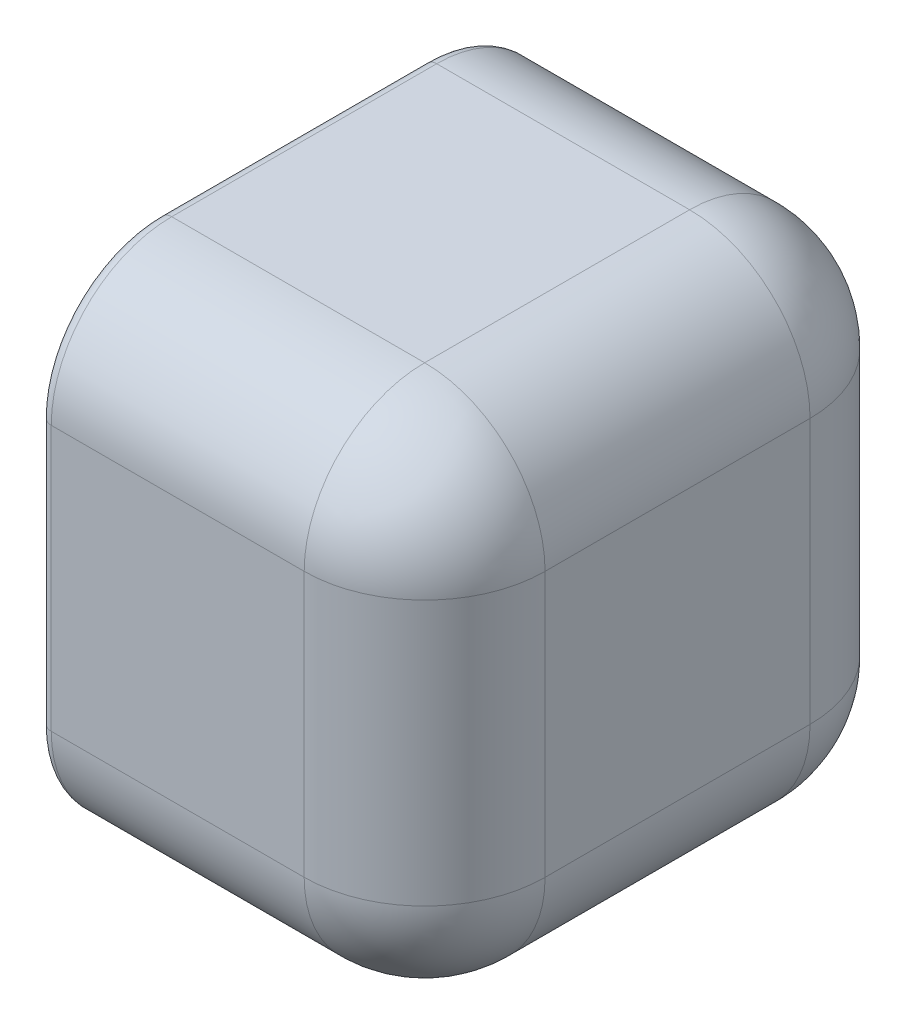
SolidWorks part; units mm, degrees
ref_plane "Plan de face" through (0, 0, 0) normal (0, 0, 1) x (1, 0, 0)
ref_plane "Plan de dessus" through (0, 0, 0) normal (0, 1, 0) x (1, 0, 0)
ref_plane "Plan de droite" through (0, 0, 0) normal (1, 0, 0) x (0, 0, -1)
sketch "Esquisse1" plane through (0, 0, 0) normal (0, 0, 1) x (1, 0, 0)
  line L1 (-21, -21) -> (21, -21)
  line L2 (-21, -21) -> (-21, 21)
  line L3 (-21, 21) -> (21, 21)
  line L4 (21, -21) -> (21, 21)
  line L5 (-21, -21) -> (21, 21) construction
  line L6 (-21, 21) -> (21, -21) construction
  point P0 (0, 0)
  dimension "D1" = 42
  dimension "D2" = 42
extrude "Boss.-Extru.1" add sketch "Esquisse1" along normal blind 42
fillet "Congé1" radius 10 12 edges at (0, -21, 0) (-21, -21, 21) (-21, 0, 0) (-21, 21, 21) (0, -21, 42) (-21, 0, 42) (21, 0, 42) (21, -21, 21) (21, 0, 0) (21, 21, 21) (0, 21, 42) (0, 21, 0)
sketch "Esquisse2" plane through (0, 0, 0) normal (0, 0, -1) x (-1, 0, 0)
  line L1 (5, -8) -> (-5, -8)
  line L2 (5, -8) -> (5, 8)
  line L3 (5, 8) -> (-5, 8)
  line L4 (-5, -8) -> (-5, 8)
  line L5 (5, -8) -> (-5, 8) construction
  line L6 (5, 8) -> (-5, -8) construction
  line L9 (1.55, -7) -> (-1.55, -7)
  line L10 (1.55, -7) -> (1.55, 7)
  line L11 (1.55, 7) -> (-1.55, 7)
  line L12 (-1.55, -7) -> (-1.55, 7)
  line L13 (1.55, -7) -> (-1.55, 7) construction
  line L14 (1.55, 7) -> (-1.55, -7) construction
  point P0 (0, 0)
  point P19 (0, 0)
  dimension "D1" = 16
  dimension "D2" = 10
  dimension "D3" = 14
  dimension "D4" = 3.1
sketch "Esquisse10" plane through (0, -21, 0) normal (0, -1, 0) x (-1, 0, 0)
  line L1 (11, -42) -> (21.1405, -42)
  line L2 (11, -42) -> (11, 0)
  line L3 (11, 0) -> (21.1405, 0)
  line L4 (21.1405, -42) -> (21.1405, 0)
  line L5 (11, -42) -> (21.1405, 0) construction
  line L6 (11, 0) -> (21.1405, -42) construction
  point P5 (16.0702, -21)
extrude "Enlèv. mat.-Extru.1" cut sketch "Esquisse10" against normal through all
sketch "Esquisse12" plane through (-11, 0, 0) normal (-1, 0, 0) x (0, 0, 1)
  line L0 (2.9289, 18.0711) -> (2.9289, -18.0711)
  line L1 (2.9289, -18.0711) -> (39.0711, -18.0711)
  line L2 (39.0711, -18.0711) -> (39.0711, 18.0711)
  line L3 (39.0711, 18.0711) -> (2.9289, 18.0711)
  line L5 (2.9289, 18.0711) -> (5.9289, 18.0711)
  line L6 (2.9289, 18.0711) -> (2.9289, 15.0711)
  line L7 (2.9289, 15.0711) -> (5.9289, 15.0711)
  line L8 (5.9289, 18.0711) -> (5.9289, 15.0711)
  line L9 (2.9289, 18.0711) -> (5.9289, 15.0711) construction
  line L10 (2.9289, 15.0711) -> (5.9289, 18.0711) construction
  line L11 (39.0711, -18.0711) -> (36.0711, -18.0711)
  line L12 (39.0711, -18.0711) -> (39.0711, -15.0711)
  line L13 (39.0711, -15.0711) -> (36.0711, -15.0711)
  line L14 (36.0711, -18.0711) -> (36.0711, -15.0711)
  line L15 (39.0711, -18.0711) -> (36.0711, -15.0711) construction
  line L16 (39.0711, -15.0711) -> (36.0711, -18.0711) construction
  arc A0 (10, 21) -> (0, 11) centre (10, 11) ccw construction
  arc A1 (0, -11) -> (10, -21) centre (10, -11) ccw construction
  arc A2 (32, -21) -> (42, -11) centre (32, -11) ccw construction
  arc A3 (42, 11) -> (32, 21) centre (32, 11) ccw construction
  point P19 (4.4289, 16.5711)
  point P23 (37.5711, -16.5711)
  dimension "D1" = 3
  dimension "D2" = 3
  dimension "D3" = 3
  dimension "D4" = 3
sketch "Esquisse14" plane through (-11, 0, 0) normal (-1, 0, 0) x (0, 0, 1)
  line L1 (5.9289, 15.0711) -> (36.0711, 15.0711)
  line L2 (5.9289, 15.0711) -> (5.9289, -15.0711)
  line L3 (5.9289, -15.0711) -> (36.0711, -15.0711)
  line L4 (36.0711, 15.0711) -> (36.0711, -15.0711)
  line L5 (5.9289, 15.0711) -> (36.0711, -15.0711) construction
  line L6 (5.9289, -15.0711) -> (36.0711, 15.0711) construction
  point P4 (21, 0)
extrude "Enlèv. mat.-Extru.5" cut sketch "Esquisse2" against normal blind 8 contours L10 L9 L12 L11
extrude "Enlèv. mat.-Extru.6" cut sketch "Esquisse14" against normal blind 22
sketch "Esquisse17" plane through (11, 0, 0) normal (-1, 0, 0) x (0, 0, 1)
  line L1 (5.9289, 15.0711) -> (9.9289, 15.0711)
  line L2 (5.9289, 15.0711) -> (5.9289, 11.0711)
  line L3 (5.9289, 11.0711) -> (9.9289, 11.0711)
  line L4 (9.9289, 15.0711) -> (9.9289, 11.0711)
  line L5 (5.9289, 15.0711) -> (9.9289, 11.0711) construction
  line L6 (5.9289, 11.0711) -> (9.9289, 15.0711) construction
  line L7 (36.0711, -15.0711) -> (32.0711, -15.0711)
  line L8 (36.0711, -15.0711) -> (36.0711, -11.5711)
  line L9 (36.0711, -11.5711) -> (32.0711, -11.5711)
  line L10 (32.0711, -15.0711) -> (32.0711, -11.5711)
  line L11 (36.0711, -15.0711) -> (32.0711, -11.5711) construction
  line L12 (36.0711, -11.5711) -> (32.0711, -15.0711) construction
  point P4 (7.9289, 13.0711)
  point P10 (34.0711, -13.3211)
  dimension "D1" = 4
  dimension "D2" = 4
  dimension "D3" = 4
  dimension "D4" = 3.5
sketch "Esquisse20" plane through (11, 0, 0) normal (-1, 0, 0) x (0, 0, 1)
  line L1 (36.0711, 15.0711) -> (32.0711, 15.0711)
  line L2 (36.0711, 15.0711) -> (36.0711, 11.5711)
  line L3 (36.0711, 11.5711) -> (32.0711, 11.5711)
  line L4 (32.0711, 15.0711) -> (32.0711, 11.5711)
  line L5 (36.0711, 15.0711) -> (32.0711, 11.5711) construction
  line L6 (36.0711, 11.5711) -> (32.0711, 15.0711) construction
  point P4 (34.0711, 13.3211)
  dimension "D1" = 3.5
  dimension "D2" = 4
sketch "Esquisse21" plane through (11, 0, 0) normal (-1, 0, 0) x (0, 0, 1)
  line L1 (36.0711, -15.0711) -> (29.0711, -15.0711)
  line L2 (36.0711, -15.0711) -> (36.0711, -8.0711)
  line L3 (36.0711, -8.0711) -> (29.0711, -8.0711)
  line L4 (29.0711, -15.0711) -> (29.0711, -8.0711)
  line L5 (36.0711, -15.0711) -> (29.0711, -8.0711) construction
  line L6 (36.0711, -8.0711) -> (29.0711, -15.0711) construction
  line L7 (36.0711, 15.0711) -> (29.0711, 15.0711)
  line L8 (36.0711, 15.0711) -> (36.0711, 8.0711)
  line L9 (36.0711, 8.0711) -> (29.0711, 8.0711)
  line L10 (29.0711, 15.0711) -> (29.0711, 8.0711)
  line L11 (36.0711, 15.0711) -> (29.0711, 8.0711) construction
  line L12 (36.0711, 8.0711) -> (29.0711, 15.0711) construction
  point P4 (32.5711, -11.5711)
  point P10 (32.5711, 11.5711)
  dimension "D1" = 7
  dimension "D2" = 7
  dimension "D3" = 7
  dimension "D4" = 7
extrude "Boss.-Extru.2" add sketch "Esquisse21" along normal blind 20
sketch "Esquisse24" plane through (11, 0, 0) normal (-1, 0, 0) x (0, 0, 1)
  circle A0 centre (32.0711, 11.5711) radius 1.675
  circle A1 centre (32.0711, -11.5711) radius 1.675
extrude "Enlèv. mat.-Extru.8" cut sketch "Esquisse24" along normal blind 26
fillet "Congé2" radius 1 44 edges at (-9, 15.0711, 32.5711) (-11, 15.0711, 21) (1, -15.0711, 29.0711) (-11, 18.0711, 2.9289) (-11, 0, 0) (-11, -18.0711, 2.9289) (-11, -21, 21) (-11, -18.0711, 39.0711) (-11, 0, 42) (-11, 18.0711, 39.0711) (-9, 11.5711, 36.0711) (-11, 0, 36.0711) (-9, -11.5711, 36.0711) (1, -8.0711, 36.0711) (1, 8.0711, 36.0711) (11, 0, 36.0711) (11, -8.0711, 32.5711) (11, -11.5711, 29.0711) (11, -15.0711, 17.5) (11, 0, 5.9289) (11, 15.0711, 17.5) (11, 11.5711, 29.0711) (11, 8.0711, 32.5711) (-11, 21, 21) (0, -7, 0) (-1.55, 0, 0) (0, 7, 0) (1.55, 0, 0) (0, -7, 5.9289) (1.55, 0, 5.9289) (-1.55, 0, 5.9289) (0, 7, 5.9289) (1, 15.0711, 29.0711) (0, -15.0711, 5.9289) (0, 15.0711, 5.9289) (-11, 0, 5.9289) (-11, -15.0711, 21) (-9, -15.0711, 32.5711) (-9, -11.5711, 29.0711) (-9, -8.0711, 32.5711) (-9, 11.5711, 29.0711) (-9, 8.0711, 32.5711) (1, -8.0711, 29.0711) (1, 8.0711, 29.0711)
sketch "Esquisse27" plane through (0, 0, 0) normal (0, 0, -1) x (-1, 0, 0)
  line L1 (-7.5, -7.5) -> (7.5, -7.5)
  line L2 (-7.5, -7.5) -> (-7.5, 7.5)
  line L3 (-7.5, 7.5) -> (7.5, 7.5)
  line L4 (7.5, -7.5) -> (7.5, 7.5)
  line L5 (-7.5, -7.5) -> (7.5, 7.5) construction
  line L6 (-7.5, 7.5) -> (7.5, -7.5) construction
  circle A0 centre (-7.5, 7.5) radius 2.375
  circle A1 centre (7.5, 7.5) radius 2.375
  circle A2 centre (-7.5, -7.5) radius 2.375
  circle A3 centre (7.5, -7.5) radius 2.375
  point P0 (0, 0)
  dimension "D1" = 15
  dimension "D2" = 15
extrude "Enlèv. mat.-Extru.9" cut sketch "Esquisse27" against normal blind 10 contours L4 A1 L3 | L3 A0 L2 | L2 A2 L1 | L3 A1 L4 | L2 A0 L3 | L1 A2 L2 | A3
